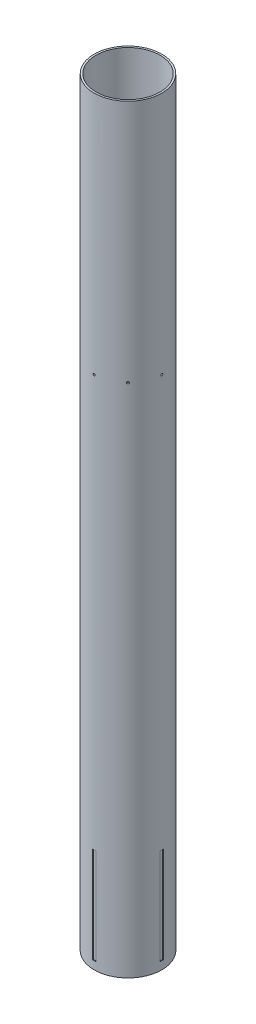
SolidWorks part; units mm, degrees
material "Hexcel AS4C (3000 Filaments)"
ref_plane "Front Plane" through (0, 0, 0) normal (0, 0, 1) x (1, 0, 0)
ref_plane "Top Plane" through (0, 0, 0) normal (0, 1, 0) x (1, 0, 0)
ref_plane "Right Plane" through (0, 0, 0) normal (1, 0, 0) x (0, 0, -1)
sketch "Sketch1" plane through (0, 0, 0) normal (0, 1, 0) x (1, 0, 0)
  circle A0 centre (0, 0) radius 50.8
  dimension "D1" = 101.6
extrude "Body Tube Extrusion" add sketch "Sketch1" along normal blind 1206.5 thin thin type one direction wall 2.921
ref_plane "Plane1" through (0, 0, 53.721) normal (0, 0, 1) x (1, 0, 0)
sketch "Sketch2" plane through (0, 0, 53.721) normal (0, 0, 1) x (1, 0, 0)
  line L0 (0, 1206.5) -> (0, 0) construction
  line L1 (50.8, 1206.5) -> (-50.8, 1206.5) construction
  line L2 (-53.721, 0) -> (53.721, 0) construction
  circle A0 centre (0, 819.15) radius 1.6383
  dimension "D1" = 3.2766
  dimension "D2" = 819.15
extrude "Engine Block Hole" cut sketch "Sketch2" against normal up to next
pattern_circular "CirPattern1" count 8 over 360 about axis through (0, 1206.5, 0) along (0, -1, 0) of "Engine Block Hole"
sketch "Sketch3" plane through (0, 0, 53.721) normal (0, 0, 1) x (1, 0, 0)
  line L0 (0, 0) -> (0, 12.7) construction
  line L1 (-50.8, 0) -> (50.8, 0) construction
  line L2 (0, 1206.5) -> (0, 0) construction
  line L4 (-2.667, 165.1) -> (2.667, 165.1)
  line L5 (-2.667, 165.1) -> (-2.667, 12.7)
  line L6 (-2.667, 12.7) -> (2.667, 12.7)
  line L7 (2.667, 165.1) -> (2.667, 12.7)
  point P10 (0, 12.7)
  dimension "D1" = 152.4
  dimension "D2" = 5.334
  dimension "D3" = 12.7
extrude "Cut-Extrude1" cut sketch "Sketch3" against normal blind 1.27
pattern_circular "CirPattern2" count 4 over 360 about axis through (0, 1206.5, 0) along (0, -1, 0) of "Cut-Extrude1" reverse direction yes
